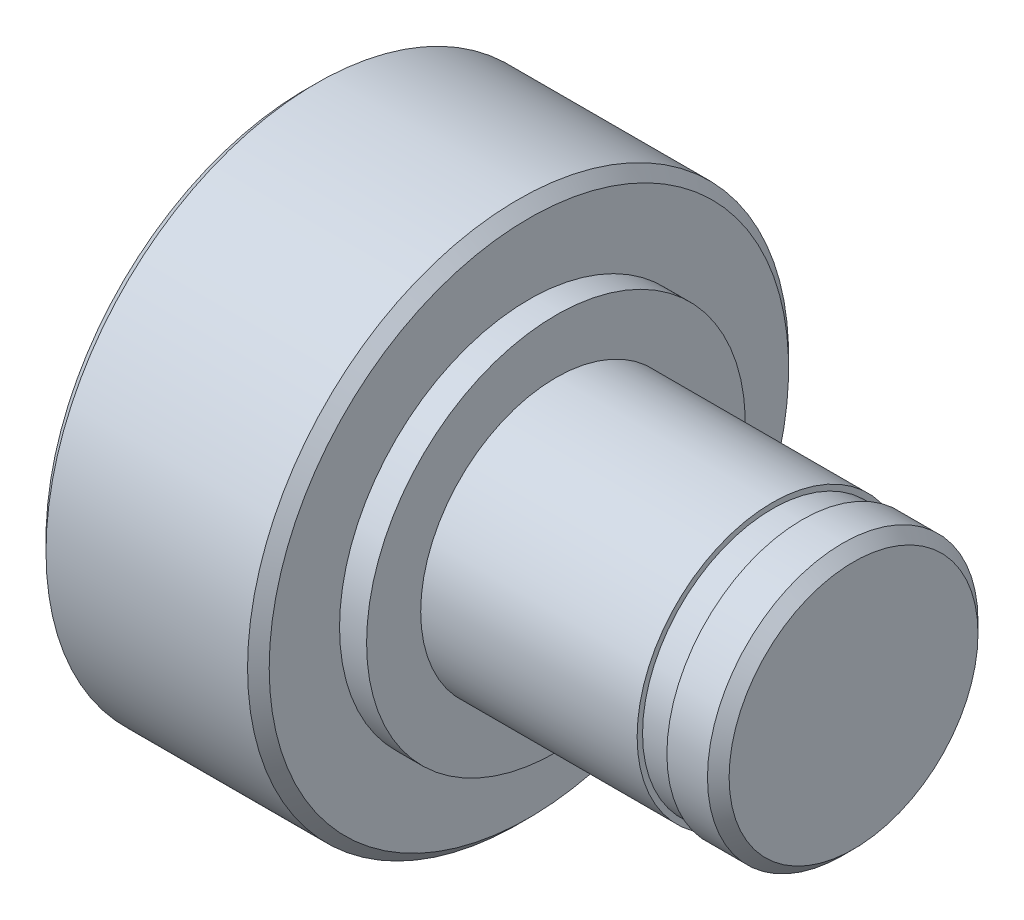
SolidWorks part; units mm, degrees
material "1060 Alloy"
ref_plane "Front Plane" through (0, 0, 0) normal (0, 0, 1) x (1, 0, 0)
ref_plane "Top Plane" through (0, 0, 0) normal (0, 1, 0) x (1, 0, 0)
ref_plane "Right Plane" through (0, 0, 0) normal (1, 0, 0) x (0, 0, -1)
sketch "Sketch1" plane through (0, 0, 0) normal (0, 1, 0) x (1, 0, 0)
  line L0 (0, 0) -> (20.25, 0) construction
  line L1 (0, 0) -> (0, 10)
  line L2 (0, 10) -> (8.25, 10)
  line L3 (8.25, 10) -> (8.25, 7)
  line L4 (9.25, 5) -> (20.25, 5)
  line L5 (20.25, 5) -> (20.25, 0)
  line L6 (8.25, 7) -> (9.25, 7)
  line L7 (9.25, 7) -> (9.25, 5)
  line L8 (0, 0) -> (20.25, 0)
  dimension "D1" = 20
  dimension "D2" = 10
  dimension "D3" = 8.25
  dimension "D4" = 2
  dimension "D5" = 1
  dimension "D6" = 11
revolve "Revolve1" add sketch "Sketch1" angle 360 about L0
chamfer "Chamfer1" distance 0.4 angle 45 3 edges at (8.25, 0, 10) (20.25, 0, 5) (0, 0, 10)
sketch "Sketch2" plane through (0, 0, 0) normal (0, 1, 0) x (1, 0, 0)
  line L0 (17.25, 5) -> (17.25, 4.8)
  line L1 (19.85, 5) -> (9.25, 5) construction
  line L2 (17.25, 4.8) -> (18.35, 4.8)
  line L3 (18.35, 4.8) -> (18.35, 5)
  line L4 (19.85, 5) -> (9.25, 5) construction
  line L5 (18.35, 5) -> (17.25, 5)
  line L6 (9.25, 0) -> (19.85, 0) construction
  line L7 (9.25, -5) -> (9.25, 5) construction
  line L8 (19.85, -5) -> (19.85, 5) construction
  dimension "D1" = 9.6
  dimension "D2" = 1.1
  dimension "D3" = 8
revolve "Cut-Revolve1" cut sketch "Sketch2" angle 360 about L6
